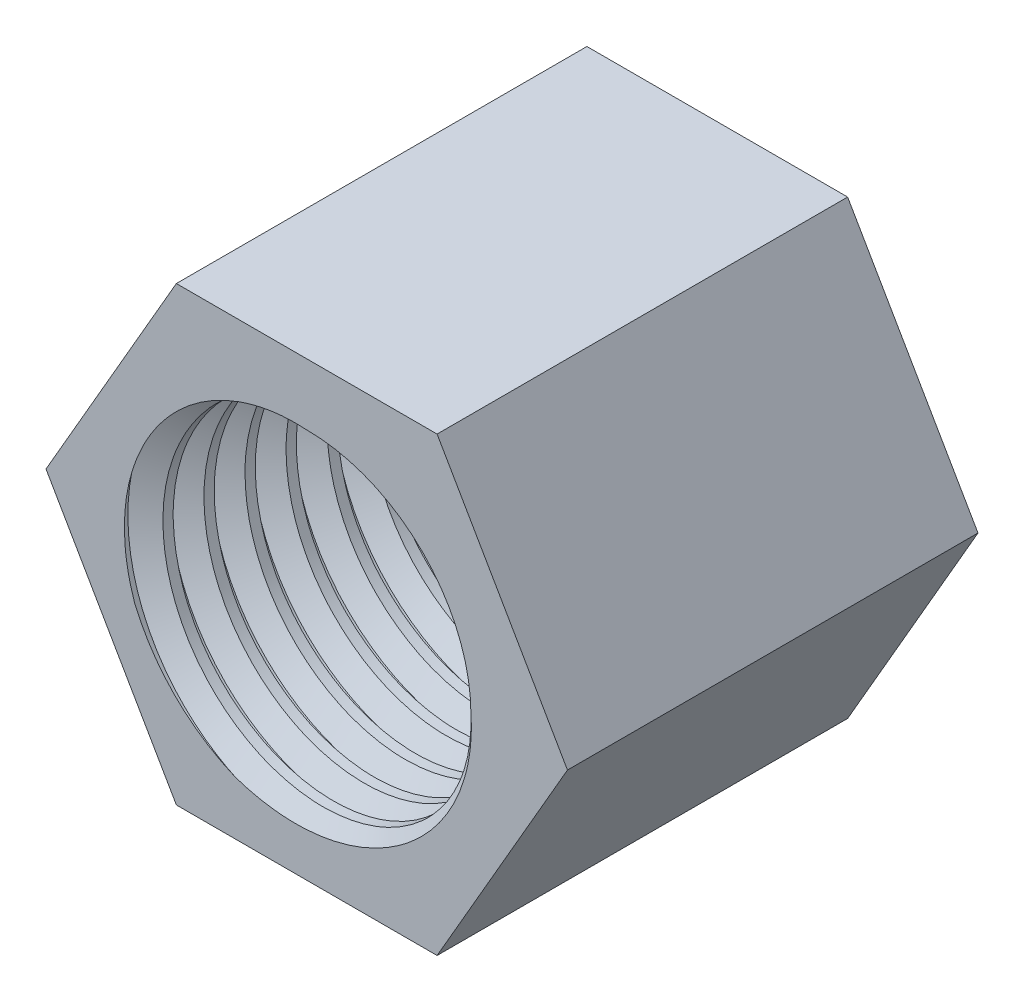
SolidWorks part; units mm, degrees
material "Brass"
ref_plane "Front Plane" through (0, 0, 0) normal (0, 0, 1) x (1, 0, 0)
ref_plane "Top Plane" through (0, 0, 0) normal (0, 1, 0) x (1, 0, 0)
ref_plane "Right Plane" through (0, 0, 0) normal (1, 0, 0) x (0, 0, -1)
sketch "Sketch1" plane through (0, 0, 0) normal (0, 0, 1) x (1, 0, 0)
  line L1 (6.3509, 0) -> (3.1754, 5.5)
  line L2 (3.1754, 5.5) -> (-3.1754, 5.5)
  line L3 (-3.1754, 5.5) -> (-6.3509, 0)
  line L4 (-6.3509, 0) -> (-3.1754, -5.5)
  line L5 (-3.1754, -5.5) -> (3.1754, -5.5)
  line L6 (3.1754, -5.5) -> (6.3509, 0)
  circle A0 centre (0, 0) radius 5.5 construction
  dimension "D1" = 11
extrude "Boss-Extrude1" add sketch "Sketch1" along normal blind 10
sketch "Sketch2" plane through (0, 0, 10) normal (0, 0, 1) x (1, 0, 0)
  circle A0 centre (0, 0) radius 4
extrude "Cut-Extrude1" cut sketch "Sketch2" against normal blind 7
sketch "Sketch3" plane through (0, 0, 3) normal (0, 0, 1) x (1, 0, 0)
  circle A0 centre (0, 0) radius 3
extrude "Cut-Extrude2" cut sketch "Sketch3" against normal through all
thread "Thread2" pitch 1 method cut profile "Thread Profile3" start angle 0, offset 0, length 0, pitch 1, diameter 8
ref_plane "Plane3" through (4, 0, 3) normal (0, -1, 0) x (1, 0, 0)
sketch "Thread Profile3" plane through (4, 0, 3) normal (0, -1, 0) x (1, 0, 0)
  line L0 (0, 0) -> (0, 1) construction
  line L1 (0, 0) -> (0.5413, 0.3125)
  line L2 (0.5413, 0.3125) -> (0.5413, 0.4375)
  line L3 (0.5413, 0.4375) -> (0, 0.75)
  line L4 (0.5413, 0.375) -> (0, 0.375) construction
  line L11 (0, 0) -> (0, 0.75)
  point P2 (0, 0)
  dimension "Pitch" = 1
  dimension "Profile_Angle" = 60
  dimension "Profile_Land" = 0.125
  dimension "Profile_Height" = 0.5413
